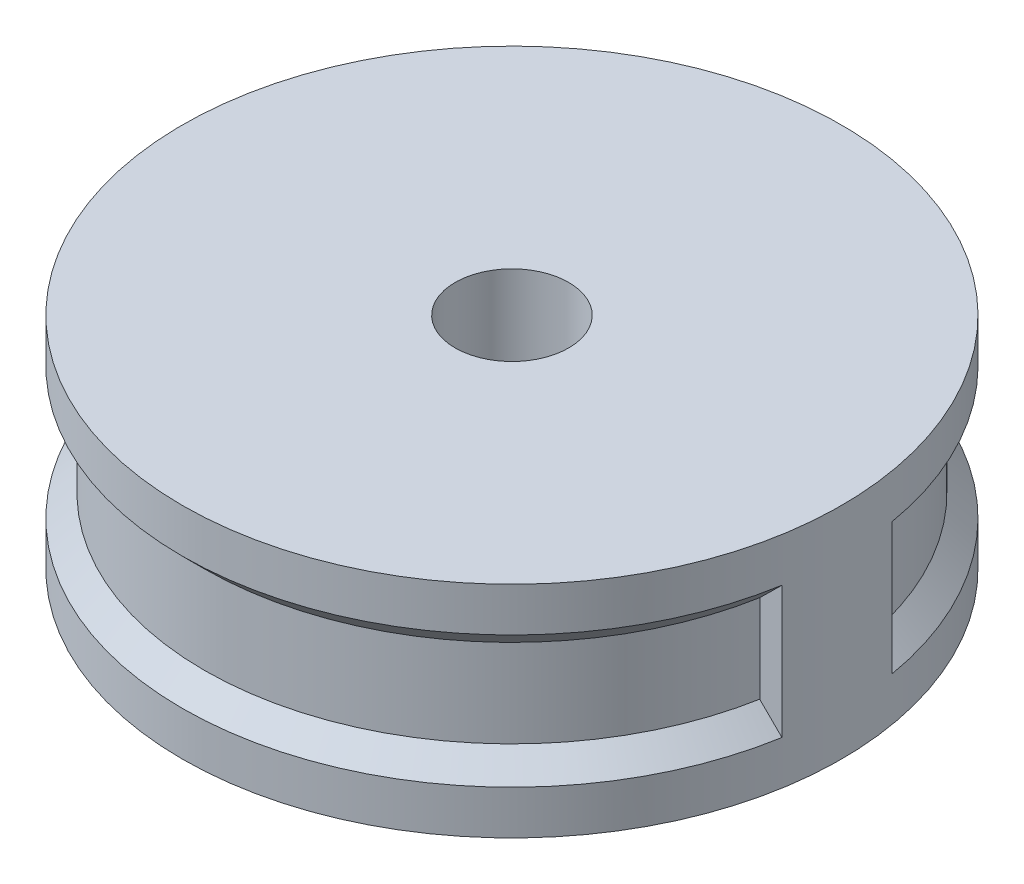
SolidWorks part; units mm, degrees
ref_plane "Front Plane" through (0, 0, 0) normal (0, 0, 1) x (1, 0, 0)
ref_plane "Top Plane" through (0, 0, 0) normal (0, 1, 0) x (1, 0, 0)
ref_plane "Right Plane" through (0, 0, 0) normal (1, 0, 0) x (0, 0, -1)
sketch "Sketch1" plane through (0, 0, 0) normal (0, 1, 0) x (1, 0, 0)
  circle A0 centre (0, 0) radius 15
  circle A1 centre (0, 0) radius 14
  circle A2 centre (0, 0) radius 2.585
  dimension "D1" = 30
  dimension "D2" = 1
  dimension "D3" = 5.17
extrude "Boss-Extrude1" add sketch "Sketch1" along normal blind 10 contours A1 region at (-13.604, 0, 0)
extrude "Boss-Extrude2" add sketch "Sketch1<3>" along normal blind 2 contours A0 A1 region at (-14.5757, 0, 0)
sketch "Sketch1<3>" plane through (0, 0, 0) normal (0, 1, 0) x (1, 0, 0) same geometry as "Sketch1"
extrude "Boss-Extrude3" add sketch "Sketch1<4>" against normal blind 2 from surface contours A0 A1 region at (-14.5757, 0, 0) starting at face at (0, 10, 2.585)
sketch "Sketch1<4>" plane through (0, 0, 0) normal (0, 1, 0) x (1, 0, 0) same geometry as "Sketch1"
chamfer "Chamfer1" distance 1 angle 45 2 edges at (0, 8, 14) (0, 2, 14)
sketch "Sketch2" plane through (0, 0, 0) normal (0, 1, 0) x (1, 0, 0)
  line L0 (14.7902, 2.5) -> (13.7902, 2.5)
  line L1 (13.7902, 2.5) -> (13.7902, -2.5)
  line L2 (13.7902, -2.5) -> (14.7902, -2.5)
  circle A1 centre (0, 0) radius 15 construction
  arc A2 (14.7902, 2.5) -> (14.7902, -2.5) centre (0, 0) cw
  point P4 (13.7902, 0)
  point P8 (0, 0)
  point P9 (13.6193, 0)
  point P11 (13.6193, 0)
  point P12 (13.6193, 0)
  point P13 (2.9796, 0)
  dimension "D1" = 1
  dimension "D2" = 5
extrude "Boss-Extrude4" add sketch "Sketch2" along normal through all
